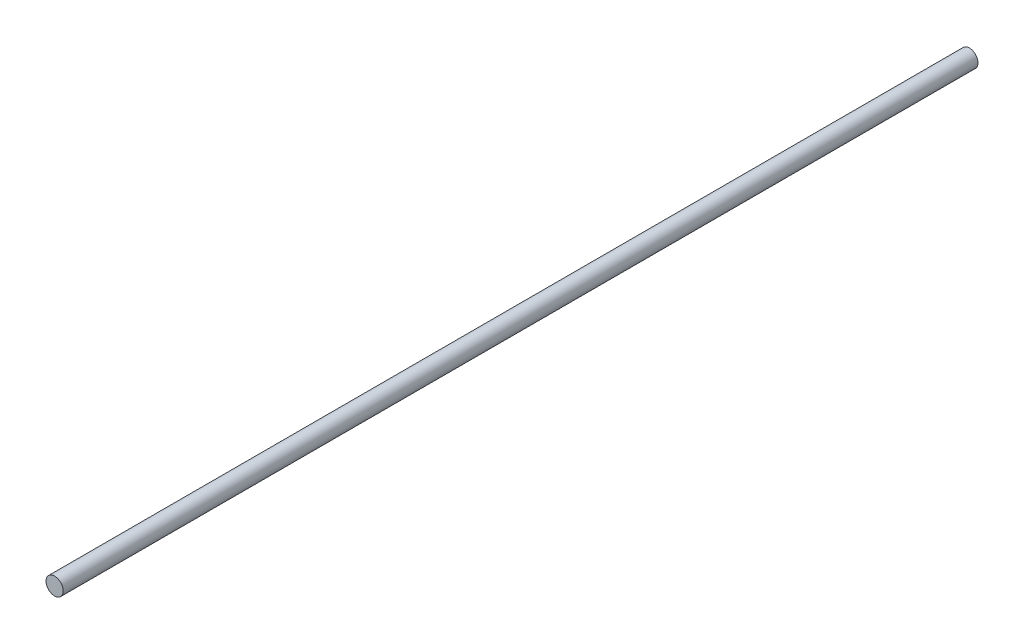
SolidWorks part; units mm, degrees
ref_plane "Front Plane" through (0, 0, 0) normal (0, 0, 1) x (1, 0, 0)
ref_plane "Top Plane" through (0, 0, 0) normal (0, 1, 0) x (1, 0, 0)
ref_plane "Right Plane" through (0, 0, 0) normal (1, 0, 0) x (0, 0, -1)
sketch "Sketch1" plane through (0, 0, 0) normal (0, 0, 1) x (1, 0, 0)
  circle A0 centre (0, 0) radius 4
  dimension "D1" = 8
extrude "Boss-Extrude1" add sketch "Sketch1" along normal blind 425
